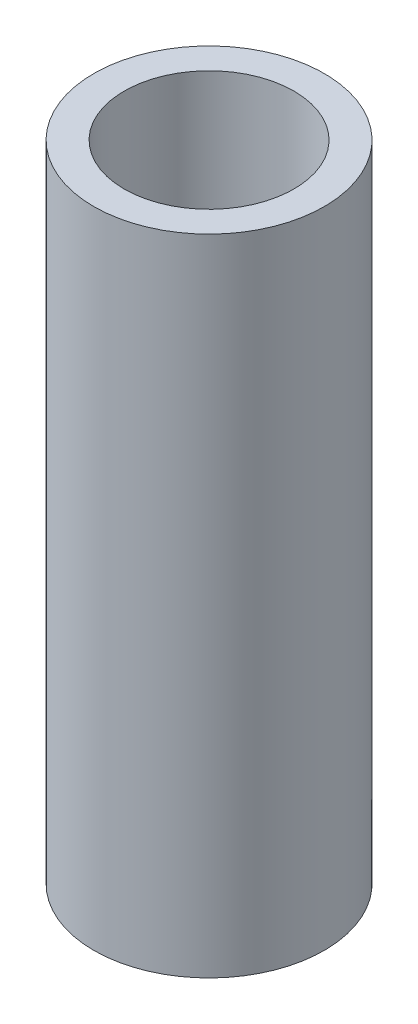
SolidWorks part; units mm, degrees
ref_plane "Front Plane" through (0, 0, 0) normal (0, 0, 1) x (1, 0, 0)
ref_plane "Top Plane" through (0, 0, 0) normal (0, 1, 0) x (1, 0, 0)
ref_plane "Right Plane" through (0, 0, 0) normal (1, 0, 0) x (0, 0, -1)
sketch "Sketch1" plane through (0, 0, 0) normal (0, 1, 0) x (1, 0, 0)
  circle A0 centre (0, 0) radius 12.5
  dimension "SLEEVE_OD" = 25
extrude "Boss-Extrude1" add sketch "Sketch1" along normal blind 69.8692
sketch "Sketch2" plane through (0, 0, 0) normal (0, 1, 0) x (1, 0, 0)
  circle A0 centre (0, 0) radius 9.2054
  dimension "BORE_D" = 18.4107
extrude "Cut-Extrude1" cut sketch "Sketch2" along normal through all
chamfer "Chamfer1" distance 2.4083 angle 60 rebuild error yes
